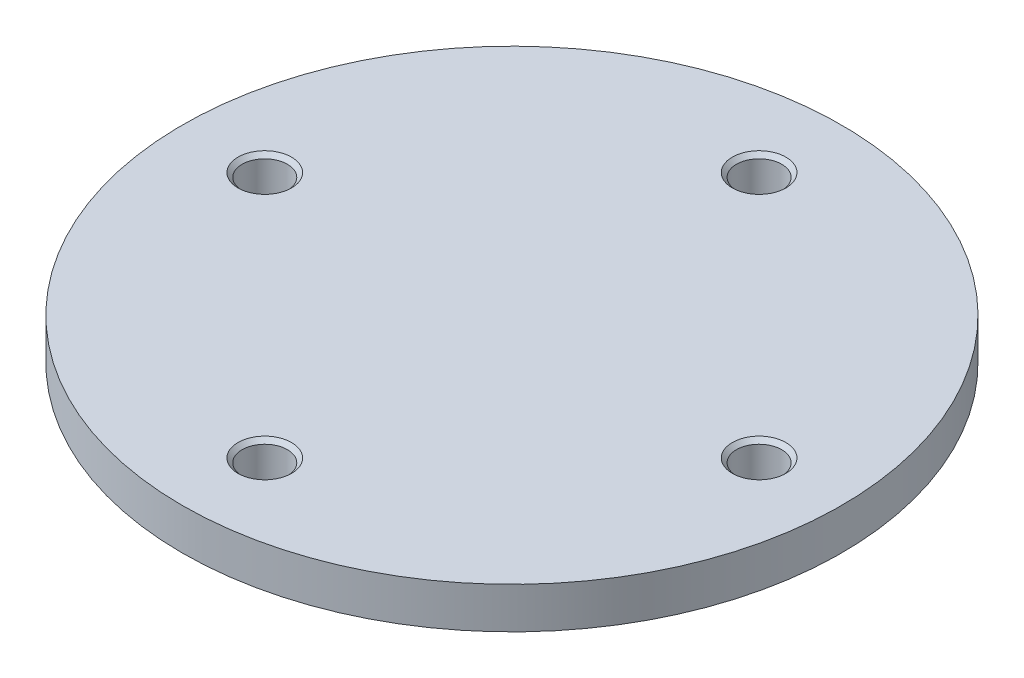
SolidWorks part; units mm, degrees
ref_plane "前视基准面" through (0, 0, 0) normal (0, 0, 1) x (1, 0, 0)
ref_plane "上视基准面" through (0, 0, 0) normal (0, 1, 0) x (1, 0, 0)
ref_plane "右视基准面" through (0, 0, 0) normal (1, 0, 0) x (0, 0, -1)
other "Configuration Table"
sketch "草图1" plane through (0, 0, 0) normal (0, 1, 0) x (1, 0, 0)
  circle A0 centre (0, 0) radius 2.5
  circle A1 centre (0, 0) radius 6
  dimension "D1" = 5
  dimension "D2" = 12
extrude "凸台-拉伸1" add sketch "草图1" along normal blind 21
sketch "草图2" plane through (0, 21, 0) normal (0, 1, 0) x (1, 0, 0)
  circle A0 centre (0, 0) radius 40
  dimension "D1" = 80
extrude "凸台-拉伸2" add sketch "草图2" along normal blind 5
chamfer "倒角1" distance 10 angle 45 1 edges at (0, 21, 6)
sketch "草图3" plane through (0, 26, 0) normal (0, 1, 0) x (1, 0, 0)
  circle A0 centre (0, 0) radius 30 construction
  circle A1 centre (0, 30) radius 2.75
  circle A2 centre (30, 0) radius 2.75
  circle A3 centre (0, -30) radius 2.75
  circle A4 centre (-30, 0) radius 2.75
  point P14 (0, 0)
  dimension "D1" = 60
  dimension "D2" = 5.5
  dimension "D3" = 4
extrude "切除-拉伸2" cut sketch "草图3" against normal blind 5
chamfer "倒角2" distance 0.5 angle 45 4 edges at (0, 26, 32.75) (-30, 26, 2.75) (0, 26, -27.25) (30, 26, 2.75)
